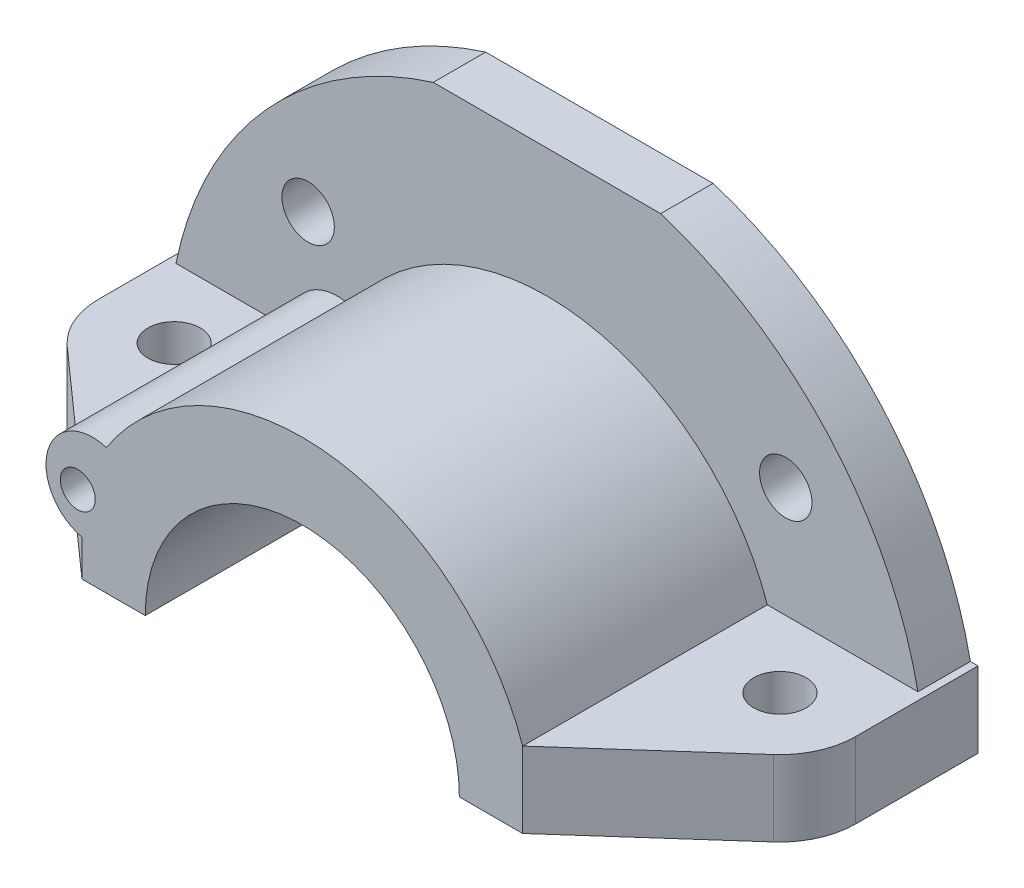
SolidWorks part; units mm, degrees
note: The reader was unsure of these and kept them because the rebuilt part matched: shared geometry of "Sketch2<4>", "Sketch2<5>", "Sketch3<4>".
material "Chromium Copper, UNS C18200"
ref_plane "Front Plane" through (0, 0, 0) normal (0, 0, 1) x (1, 0, 0)
ref_plane "Top Plane" through (0, 0, 0) normal (0, 1, 0) x (1, 0, 0)
ref_plane "Right Plane" through (0, 0, 0) normal (1, 0, 0) x (0, 0, -1)
sketch "Sketch2" plane through (0, 0, 0) normal (0, 0, 1) x (1, 0, 0)
  line L0 (0, 0) -> (28319.7461, 0) construction
  line L1 (0, 0) -> (0, 28319.7461) construction
  line L2 (37.8286, 13) -> (65, 13)
  line L3 (-65, 0) -> (65, 0)
  line L4 (-65, 0) -> (-65, 13)
  line L5 (-65, 13) -> (-37.8286, 13)
  line L6 (65, 0) -> (65, 13)
  line L7 (-19.5192, 62) -> (19.5192, 62)
  arc A0 (26.965, 0) -> (-26.965, 0) centre (0, 0) ccw
  arc A1 (40, 0) -> (-40, 0) centre (0, 0) ccw
  arc A2 (63.6867, 13) -> (19.5192, 62) centre (0, 0) ccw
  circle A3 centre (-41, 32) radius 4.5
  circle A4 centre (41, 32) radius 4.5
  arc A5 (-19.5192, 62) -> (-63.6867, 13) centre (0, 0) ccw
  dimension "D1" = 65
  dimension "D2" = 40
  dimension "D3" = 53.93
  dimension "D8" = 9
  dimension "D4" = 65
  dimension "D5" = 13
  dimension "D6" = 32
  dimension "D7" = 41
  dimension "D9" = 62
extrude "Boss-Extrude1" add sketch "Sketch2" along normal blind 51 contours L3 A1 A0
extrude "Boss-Extrude3" add sketch "Sketch2<4>" along normal blind 51 contours A1 L5 L4 L3 | A1 L3 L6 L2
sketch "Sketch2<4>" plane through (0, 0, 0) normal (0, 0, 1) x (1, 0, 0) same geometry as "Sketch2"
extrude "Boss-Extrude4" add sketch "Sketch2<5>" along normal blind 9 contours L7 A5 L5 A1 L2 A2 A4 A3
sketch "Sketch2<5>" plane through (0, 0, 0) normal (0, 0, 1) x (1, 0, 0) same geometry as "Sketch2"
sketch "Sketch3" plane through (0, 0, 0) normal (0, 1, 0) x (1, 0, 0)
  line L0 (0, 0) -> (0, -50000) construction
  line L1 (0, 0) -> (50000, 0) construction
  line L3 (65, -51) -> (65, 0) construction
  line L4 (37.8286, -51) -> (65, -51) construction
  line L5 (65, -51) -> (65, 0)
  line L6 (37.8286, -51) -> (65, -51)
  line L7 (37.8286, -51) -> (60.639, -30.7143)
  line L8 (-37.8286, -51) -> (-60.639, -30.7143)
  arc A0 (60.639, -30.7143) -> (65, -21) centre (52, -21) ccw
  circle A1 centre (52, -21) radius 4.5
  arc A2 (-60.639, -30.7143) -> (-65, -21) centre (-52, -21) cw
  circle A3 centre (-52, -21) radius 4.5
  point P17 (0, 0)
  dimension "D1" = 26
  dimension "D4" = 9
  dimension "D2" = 52
  dimension "D3" = 21
extrude "Cut-Extrude2" cut sketch "Sketch3" along normal up to next contours A0 L7 L6 L5 | A1 | A3
extrude "Cut-Extrude3" cut sketch "Sketch3<4>" along normal up to next contours L8 A2
sketch "Sketch3<4>" plane through (0, 0, 0) normal (0, 1, 0) x (1, 0, 0) same geometry as "Sketch3"
sketch "Sketch4" plane through (0, 0, 51) normal (0, 0, 1) x (1, 0, 0)
  line L0 (-37.8286, 0) -> (-26.965, 0) construction
  line L1 (0, 0) -> (0, 50000) construction
  circle A0 centre (-36, 14) radius 8
  dimension "D1" = 16
  dimension "D2" = 14
  dimension "D3" = 36
extrude "Boss-Extrude5" add sketch "Sketch4" against normal up to surface (42 mm away) up to face at (45.5, 32, 9)
hole_wizard "Ø6.0mm Dowel Hole1" positions "3DSketch1" profile "Sketch5" hole size "Ø6.0" standard "ISO"
sketch3d "3DSketch1"
  point P0 (-38.545, 12.9382, 51)
sketch "Sketch5" plane through (-38.545, 12.9382, 51) normal (1, 0, 0) x (0, -1, 0)
  line L0 (0, 0) -> (0, 14.8026)
  line L1 (0, 14.8026) -> (3, 13)
  line L2 (3, 13) -> (3, 0)
  line L5 (3, 0) -> (0, 0)
  line L10 (0, 14.8026) -> (-3, 13) construction
  line L11 (0, -6.35) -> (0, 107.95) construction
  dimension "Hole Dia." = 6
  dimension "Hole Depth" = 13
  dimension "Drill Angle" = 118
